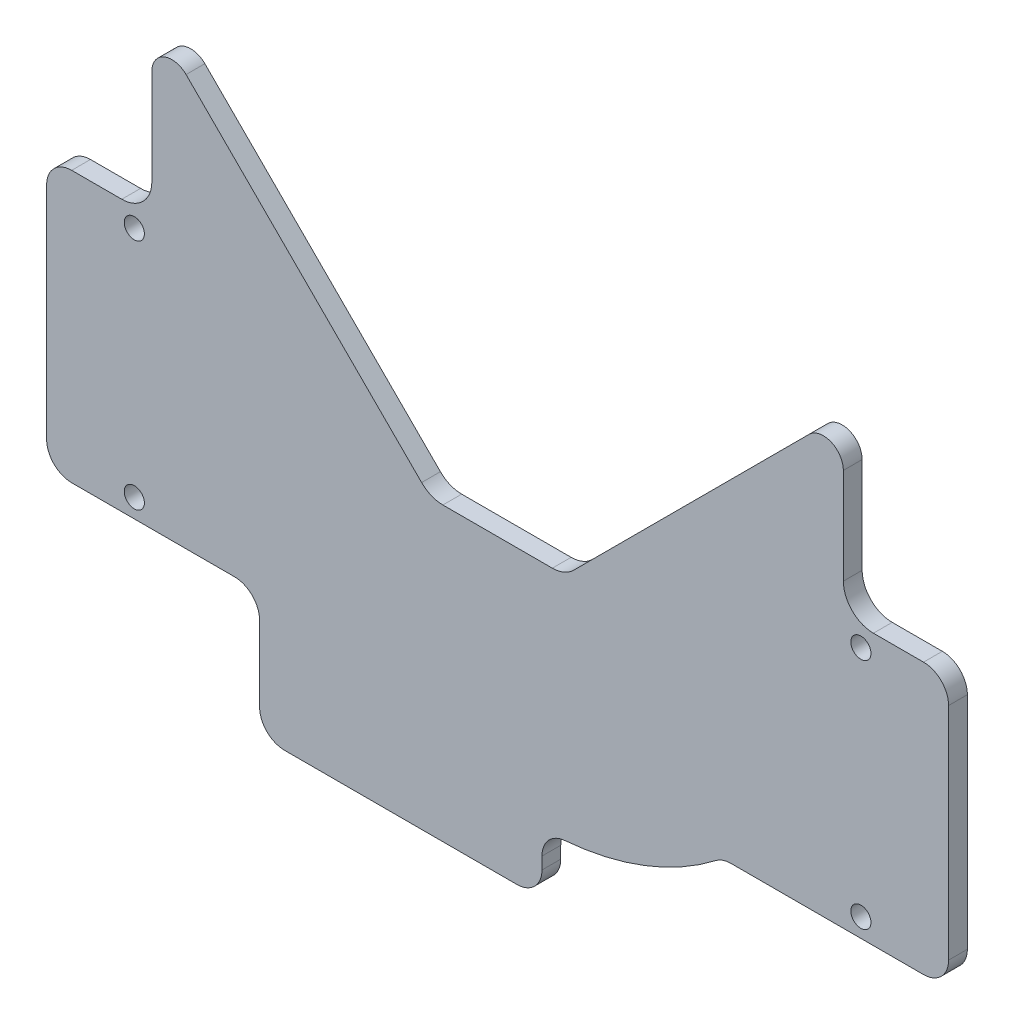
SolidWorks part; units mm, degrees
material "PET"
ref_plane "Front Plane" through (0, 0, 0) normal (0, 0, 1) x (1, 0, 0)
ref_plane "Top Plane" through (0, 0, 0) normal (0, 1, 0) x (1, 0, 0)
ref_plane "Right Plane" through (0, 0, 0) normal (1, 0, 0) x (0, 0, -1)
sketch "LayoutSke"
sketch_block_instance "Gearing 2.0-1"
sketch_block "Gearing 2.0" parameters "D5"=76.2, "D6"=25.4, "D7"=101.6, "D8"=19.05, "D1"=228.6, "D2"=123.2, "D3"=85.227, "D4"=76.454, "D9"=39.0329, "D10"=76.454, "D11"=47.625, "D12"=63.5
sketch "Sketch2" plane through (0, 0, 0) normal (0, 0, 1) x (1, 0, 0)
  line L1 (-114.3, 123.2) -> (114.3, 123.2)
  line L2 (-114.3, 123.2) -> (-114.3, -41.9)
  line L3 (-114.3, -41.9) -> (114.3, -41.9)
  line L4 (114.3, 123.2) -> (114.3, -41.9)
  dimension "D1" = 165.1
extrude "Boss-Extrude1" add sketch "Sketch2" along normal blind 4.7625
hole_wizard "1/2 (0.5) Diameter Hole1" positions "Sketch3" profile "Sketch4" hole size "1/2" standard "ANSI Inch" end condition through all
sketch "Sketch3" plane through (0, 0, 4.7625) normal (0, 0, 1) x (1, 0, 0)
  line L0 (114.3, 123.2) -> (-114.3, 123.2) construction
  point P0 (-38.227, 85.227)
  point P3 (38.227, 85.227)
  point P7 (11.2268, 45.984)
  dimension "D1" = 77.216
  dimension "D2" = 27.0002
sketch "Sketch4" plane through (-38.227, 85.227, 4.7625) normal (1, 0, 0) x (0, -1, 0)
  line L0 (0, 0) -> (0, 4.7625)
  line L1 (0, 4.7625) -> (12.7, 4.7625)
  line L2 (12.7, 4.7625) -> (12.7, 0)
  line L5 (12.7, 0) -> (0, 0)
  line L11 (0, -6.35) -> (0, 107.95) construction
  dimension "Thru Hole Dia." = 25.4
  dimension "Thru Hole Depth" = 4.7625
ref_axis "MotorShaft" through (-24.7438, -6.3341, 0) along (0, 0, 1)
ref_axis "IntermediateShaft" through (11.2395, 45.9865, 0) along (0, 0, 1)
sketch "Sketch5" plane through (0, 0, 4.7625) normal (0, 0, 1) x (1, 0, 0)
  line L0 (11.2395, 45.9865) -> (38.227, 85.227) construction
  line L10 (29.0606, 96.2614) -> (22.9081, 78.9046)
  line L11 (37.8038, 68.6601) -> (51.8105, 80.6153)
  line L12 (11.2395, 45.9865) -> (11.2395, -7.3535) construction
  arc A2 (29.0606, 96.2614) -> (51.8105, 80.6153) centre (11.2395, 45.9865) ccw
  circle A3 centre (11.2395, 45.9865) radius 50.8 construction
  arc A5 (37.8038, 68.6601) -> (22.9081, 78.9046) centre (11.2395, 45.9865) ccw
  dimension "D1" = 2.54
  dimension "D2" = 69.85
  dimension "D3" = 15
  dimension "D4" = 15
sketch "Sketch7" plane through (0, 0, 0) normal (0, 0, -1) x (-1, 0, 0)
  line L0 (-114.3, 123.2) -> (114.3, 123.2) construction
  line L1 (38.227, 85.227) -> (-38.227, 85.227) construction
  circle A0 centre (0, 180.35) radius 66.675
  point P4 (0, 123.2)
  point P6 (0, 113.675)
  dimension "D1" = 133.35
  dimension "D2" = 9.525
  dimension "D3" = 95.123
extrude "Cut-Extrude4" cut sketch "Sketch7" against normal through all
fillet "Fillet1" radius 6.35 4 edges at (-114.3, -41.9, 2.3813) (114.3, -41.9, 2.3813) (114.3, 123.2, 2.3813) (-114.3, 123.2, 2.3813)
sketch "Sketch8" plane through (0, 0, 4.7625) normal (0, 0, 1) x (1, 0, 0)
  line L0 (-107.95, -41.9) -> (107.95, -41.9) construction
  line L1 (-107.95, -41.9) -> (-60.325, -41.9)
  line L2 (-114.3, -10.15) -> (-114.3, -35.55)
  line L3 (114.3, -35.55) -> (114.3, 116.85) construction
  line L4 (-60.325, -10.15) -> (-114.3, -10.15)
  line L6 (11.2395, -41.9) -> (11.2395, -26.4035)
  line L7 (114.3, -10.15) -> (56.9451, -10.15)
  line L8 (-34.3429, 123.2) -> (-107.95, 123.2) construction
  line L9 (-114.3, 116.85) -> (-114.3, -35.55) construction
  line L11 (-60.325, -41.9) -> (-60.325, -10.15)
  line L12 (114.3, -10.15) -> (114.3, -35.55)
  line L13 (11.2395, -41.9) -> (107.95, -41.9)
  line L21 (-114.3, 59.7) -> (-95.25, 59.7) construction
  line L22 (-88.9, 66.05) -> (-88.9, 90.3562) construction
  line L23 (-78.0599, 94.8464) -> (-18.3599, 35.1464) construction
  line L24 (-13.8698, 33.2865) -> (13.8698, 33.2865) construction
  line L25 (95.25, 59.7) -> (114.3, 59.7) construction
  line L26 (88.9, 90.3562) -> (88.9, 66.05) construction
  line L27 (18.3599, 35.1464) -> (78.0599, 94.8464) construction
  line L31 (-114.3, 58.43) -> (-95.25, 58.43)
  line L32 (-87.63, 66.05) -> (-87.63, 90.3562)
  line L33 (-78.9579, 93.9484) -> (-19.2579, 34.2484)
  line L34 (-13.8698, 32.0165) -> (13.8698, 32.0165)
  line L35 (19.2579, 34.2484) -> (78.9579, 93.9484)
  line L36 (87.63, 90.3562) -> (87.63, 66.05)
  line L37 (95.25, 58.43) -> (114.3, 58.43)
  line L38 (-114.3, 58.43) -> (-114.3, 163.6461)
  line L39 (-114.3, 163.6461) -> (114.3, 163.6461)
  line L40 (114.3, 58.43) -> (114.3, 163.6461)
  arc A0 (-114.3, -35.55) -> (-107.95, -41.9) centre (-107.95, -35.55) ccw construction
  arc A1 (-114.3, -35.55) -> (-107.95, -41.9) centre (-107.95, -35.55) ccw
  arc A2 (29.0606, 96.2614) -> (51.8105, 80.6153) centre (11.2395, 45.9865) ccw construction
  arc A3 (107.95, -41.9) -> (114.3, -35.55) centre (107.95, -35.55) ccw construction
  arc A4 (107.95, -41.9) -> (114.3, -35.55) centre (107.95, -35.55) ccw
  arc A6 (11.2395, -26.4035) -> (56.9451, -10.15) centre (11.2395, 45.9865) ccw
  arc A12 (-95.25, 59.7) -> (-88.9, 66.05) centre (-95.25, 66.05) ccw construction
  arc A13 (-78.0599, 94.8464) -> (-88.9, 90.3562) centre (-82.55, 90.3562) ccw construction
  arc A14 (-18.3599, 35.1464) -> (-13.8698, 33.2865) centre (-13.8698, 39.6365) ccw construction
  arc A15 (13.8698, 33.2865) -> (18.3599, 35.1464) centre (13.8698, 39.6365) ccw construction
  arc A16 (88.9, 66.05) -> (95.25, 59.7) centre (95.25, 66.05) ccw construction
  arc A17 (88.9, 90.3562) -> (78.0599, 94.8464) centre (82.55, 90.3562) ccw construction
  arc A18 (-95.25, 58.43) -> (-87.63, 66.05) centre (-95.25, 66.05) ccw
  arc A19 (-78.9579, 93.9484) -> (-87.63, 90.3562) centre (-82.55, 90.3562) ccw
  arc A20 (-19.2579, 34.2484) -> (-13.8698, 32.0165) centre (-13.8698, 39.6365) ccw
  arc A21 (13.8698, 32.0165) -> (19.2579, 34.2484) centre (13.8698, 39.6365) ccw
  arc A22 (87.63, 90.3562) -> (78.9579, 93.9484) centre (82.55, 90.3562) ccw
  arc A23 (87.63, 66.05) -> (95.25, 58.43) centre (95.25, 66.05) ccw
  dimension "D3" = 72.39
  dimension "D1" = 133.35
  dimension "D2" = 53.975
  dimension "D4" = 103.0605
  dimension "D5" = 1.27
extrude "Cut-Extrude5" cut sketch "Sketch8" against normal through all
fillet "Fillet2" radius 6.35 9 edges at (114.3, -10.15, 2.3813) (56.9451, -10.15, 2.3813) (11.2395, -26.4035, 2.3813) (-60.325, -10.15, 2.3813) (-114.3, -10.15, 2.3813) (-60.325, -41.9, 2.3813) (11.2395, -41.9, 2.3813) (114.3, 58.43, 2.3813) (-114.3, 58.43, 2.3813)
sketch "Sketch9" plane through (0, 0, 4.7625) normal (0, 0, 1) x (1, 0, 0)
  line L0 (0, 0) -> (0, 43.6883) construction
  line L1 (-107.95, 58.43) -> (-95.25, 58.43) construction
  line L2 (-66.675, -10.15) -> (-107.95, -10.15) construction
  line L3 (-92.075, 53.6675) -> (-92.075, -5.3875) construction
  line L4 (-114.3, 52.08) -> (-114.3, -3.8) construction
  circle A0 centre (-92.075, 53.6675) radius 2.5527
  circle A1 centre (92.075, 53.6675) radius 2.5527
  circle A2 centre (92.075, -5.3875) radius 2.5527
  circle A3 centre (-92.075, -5.3875) radius 2.5527
  point P18 (0, 0)
  point P19 (0, 0)
  dimension "D1" = 4.7625
  dimension "D4" = 5.1054
  dimension "D2" = 4.7625
  dimension "D3" = 22.225
extrude "Cut-Extrude6" cut sketch "Sketch9" against normal through all
